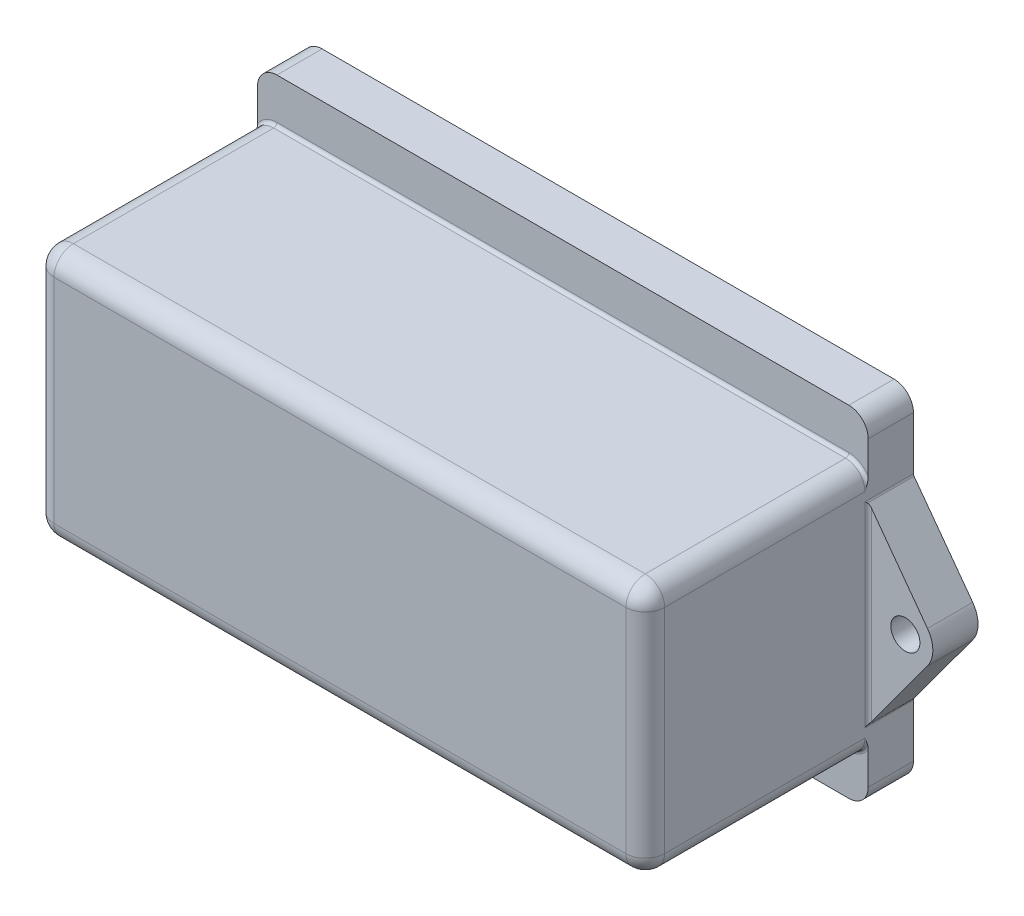
SolidWorks part; units mm, degrees
material "Custom Plastic"
ref_plane "X-Y Datum" through (0, 0, 0) normal (0, 0, 1) x (1, 0, 0)
ref_plane "X-Z Datum" through (0, 0, 0) normal (0, 1, 0) x (1, 0, 0)
ref_plane "Y-Z Datum" through (0, 0, 0) normal (1, 0, 0) x (0, 0, -1)
sketch "Sketch1" plane through (0, 0, 0) normal (0, 0, 1) x (1, 0, 0)
  line L1 (-47.25, 26.35) -> (47.25, 26.35)
  line L2 (-47.25, 26.35) -> (-47.25, -26.35)
  line L3 (-47.25, -26.35) -> (47.25, -26.35)
  line L4 (47.25, 26.35) -> (47.25, -26.35)
  line L5 (-47.25, 26.35) -> (47.25, -26.35) construction
  line L6 (-47.25, -26.35) -> (47.25, 26.35) construction
  point P0 (0, 0)
  dimension "D1" = 52.7
  dimension "D2" = 94.5
extrude "Boss-Extrude1" add sketch "Sketch1" along normal blind 7
sketch "Sketch2" plane through (0, 0, 7) normal (0, 0, 1) x (1, 0, 0)
  line L0 (-47.25, 26.35) -> (-47.25, -26.35) construction
  line L1 (-47.25, 19.5) -> (47.25, 19.5)
  line L2 (-47.25, 19.5) -> (-47.25, -19.5)
  line L3 (-47.25, -19.5) -> (47.25, -19.5)
  line L4 (47.25, 19.5) -> (47.25, -19.5)
  line L5 (-47.25, 19.5) -> (47.25, -19.5) construction
  line L6 (-47.25, -19.5) -> (47.25, 19.5) construction
  point P0 (0, 0)
  dimension "D1" = 39
extrude "Boss-Extrude2" add sketch "Sketch2" along normal blind 34.5
sketch "Sketch3" plane through (0, 0, 0) normal (0, 0, -1) x (-1, 0, 0)
  line L0 (-53, 0) -> (53, 0)
  line L1 (-47.25, 15) -> (-47.25, -15)
  line L2 (-47.25, -15) -> (-56.4246, -2.5169)
  line L3 (-47.25, 15) -> (-56.4246, 2.5169)
  line L5 (-47.25, 26.35) -> (-47.25, -26.35)
  line L6 (-47.25, -26.35) -> (47.25, -26.35)
  line L7 (47.25, -26.35) -> (47.25, 26.35)
  line L8 (47.25, 26.35) -> (-47.25, 26.35)
  line L9 (-47.25, 26.35) -> (-47.25, -26.35)
  line L10 (-47.25, -26.35) -> (47.25, -26.35)
  line L11 (47.25, -26.35) -> (47.25, 26.35)
  line L12 (47.25, 26.35) -> (-47.25, 26.35)
  circle A0 centre (-53, 0) radius 2.25
  circle A2 centre (-53, 0) radius 4.25
  point P4 (0, 0)
  point P18 (-47.25, 0)
  dimension "D2" = 4.5
  dimension "D1" = 106
  dimension "D5" = 30
  dimension "D3" = 2
  dimension "D4" = 0
extrude "Boss-Extrude3" add sketch "Sketch3" against normal blind 7
mirror "Mirror1" about plane through (0, 0, 0) normal (1, 0, 0) of "Boss-Extrude3"
fillet "Fillet1" radius 3 12 edges at (0, -19.5, 41.5) (-47.25, 0, 41.5) (0, 19.5, 41.5) (47.25, 0, 41.5) (-47.25, 19.5, 24.25) (47.25, 19.5, 24.25) (47.25, -19.5, 24.25) (-47.25, -19.5, 24.25) (-47.25, -26.35, 3.5) (-47.25, 26.35, 3.5) (47.25, 26.35, 3.5) (47.25, -26.35, 3.5) tangent propagation no
fillet "Fillet2" radius 0.5 12 edges at (-46.3713, -18.6213, 7) (46.3713, -18.6213, 7) (46.3713, 18.6213, 7) (-46.3713, 18.6213, 7) (0, -19.5, 7) (0, 19.5, 7) (47.25, 15, 3.5) (47.25, 0, 7) (47.25, -15, 3.5) (-47.25, 15, 3.5) (-47.25, 0, 7) (-47.25, -15, 3.5)
